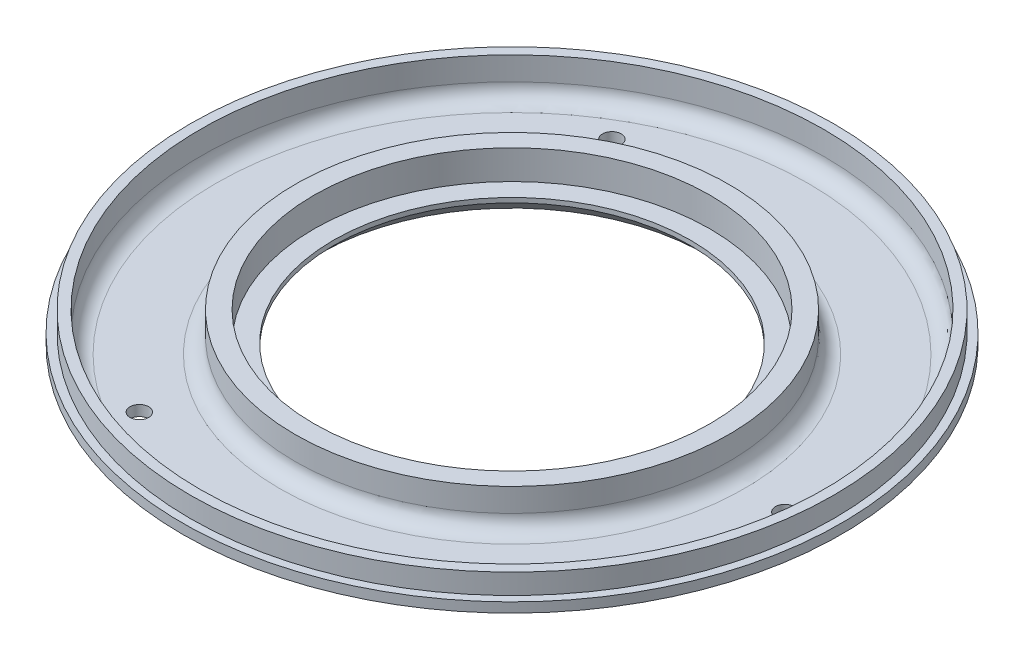
SolidWorks part; units mm, degrees
material "6061-T6 (SS)"
ref_plane "Front Plane" through (0, 0, 0) normal (0, 0, 1) x (1, 0, 0)
ref_plane "Top Plane" through (0, 0, 0) normal (0, 1, 0) x (1, 0, 0)
ref_plane "Right Plane" through (0, 0, 0) normal (1, 0, 0) x (0, 0, -1)
sketch "Sketch2" plane through (0, 0, 0) normal (1, 0, 0) x (0, 0, -1)
  line L0 (-45.8, 0) -> (-82.55, 0)
  line L1 (-82.55, 0) -> (-82.55, 12.7)
  line L2 (-82.55, 12.7) -> (-50.8, 12.7)
  line L3 (-45.8, 0) -> (-45.8, 5.2)
  line L4 (-45.8, 5.2) -> (-50.8, 5.2)
  line L5 (-50.8, 5.2) -> (-50.8, 12.7)
  line L6 (-80.2166, 12.7) -> (-80.2166, 0) construction
  dimension "D1" = 82.55
  dimension "D2" = 12.7
  dimension "D3" = 50.8
  dimension "D4" = 5
  dimension "D5" = 7.5
ref_axis "Axis1" through (0, -0.635, 0) along (0, 1, 0)
revolve "Revolve1" add sketch "Sketch2" angle 360 about axis through (0, -0.635, 0) along (0, 1, 0)
hole_wizard "#90 (0.0087) Diameter Hole1" positions "Sketch6" profile "Sketch7" hole size "#90" standard "ANSI Inch" end condition through all
sketch "Sketch6" plane through (0, 12.7, 0) normal (0, 1, 0) x (1, 0, 0)
  line L0 (0, 0) -> (-69.8201, 120.932) construction
  line L2 (0, 0) -> (0, 109.0908) construction
  point P0 (-35, 60.6218)
  dimension "D1" = 30
  dimension "D2" = 70
sketch "Sketch7" plane through (-35, 12.7, -60.6218) normal (1, 0, 0) x (0, 0, 1)
  line L0 (0, 0) -> (0, 12.7)
  line L1 (0, 12.7) -> (0.1105, 12.7)
  line L2 (0.1105, 12.7) -> (0.1105, 0)
  line L5 (0.1105, 0) -> (0, 0)
  line L11 (0, -6.35) -> (0, 107.95) construction
  dimension "Thru Hole Dia." = 0.221
  dimension "Thru Hole Depth" = 12.7
pattern_circular "CirPattern3" count 3 over 360 about axis through (0, -0.635, 0) along (0, 1, 0) of "#90 (0.0087) Diameter Hole1"
sketch "Sketch8" plane through (0, 12.7, 0) normal (0, 1, 0) x (1, 0, 0)
  circle A0 centre (0, 0) radius 55.626
  circle A1 centre (0, 0) radius 80.01
  circle A2 centre (0, 0) radius 82.55 construction
  dimension "D1" = 26.924
  dimension "D2" = 2.54
extrude "Cut-Extrude1" cut sketch "Sketch8" against normal blind 10
fillet "Fillet5" radius 4 2 edges at (0, 2.7, 55.626) (0, 2.7, 80.01)
chamfer "Chamfer1" distance 4 angle 45 1 edges at (0, 0, -45.8)
sketch "Sketch10" plane through (0, 0, 0) normal (0, -1, 0) x (1, 0, 0)
  circle A0 centre (0, 0) radius 82.55
  circle A1 centre (0, 0) radius 84.55
  circle A2 centre (0, 0) radius 82.55 construction
  dimension "D1" = 2
extrude "Boss-Extrude1" add sketch "Sketch10" against normal blind 7.5
chamfer "Chamfer3" distance 5 angle 60 1 edges at (0, 0, -84.55) first distance on face at (0, 7.5, -84.55)
fillet "Fillet4" radius 5 1 edges at (0, 0, 75.8897)
hole_wizard "#12 (0.189) Diameter Hole1" positions "Sketch13" profile "Sketch14" hole size "#12" standard "ANSI Inch" end condition through all
sketch "Sketch13" plane through (0, 0, 0) normal (0, -1, 0) x (-1, 0, 0)
  point P4 (35, 60.6218)
sketch "Sketch14" plane through (-35, 0, -60.6218) normal (1, 0, 0) x (0, 0, -1)
  line L0 (0, 0) -> (0, 12.7)
  line L1 (0, 12.7) -> (2.4003, 12.7)
  line L2 (2.4003, 12.7) -> (2.4003, 0)
  line L5 (2.4003, 0) -> (0, 0)
  line L11 (0, -6.35) -> (0, 107.95) construction
  dimension "Thru Hole Dia." = 4.8006
  dimension "Thru Hole Depth" = 12.7
pattern_circular "CirPattern5" count 3 over 360 about axis through (0, -0.635, 0) along (0, 1, 0) of "#12 (0.189) Diameter Hole1"
equation "\"TubeDiameter\" = 6.500in"
